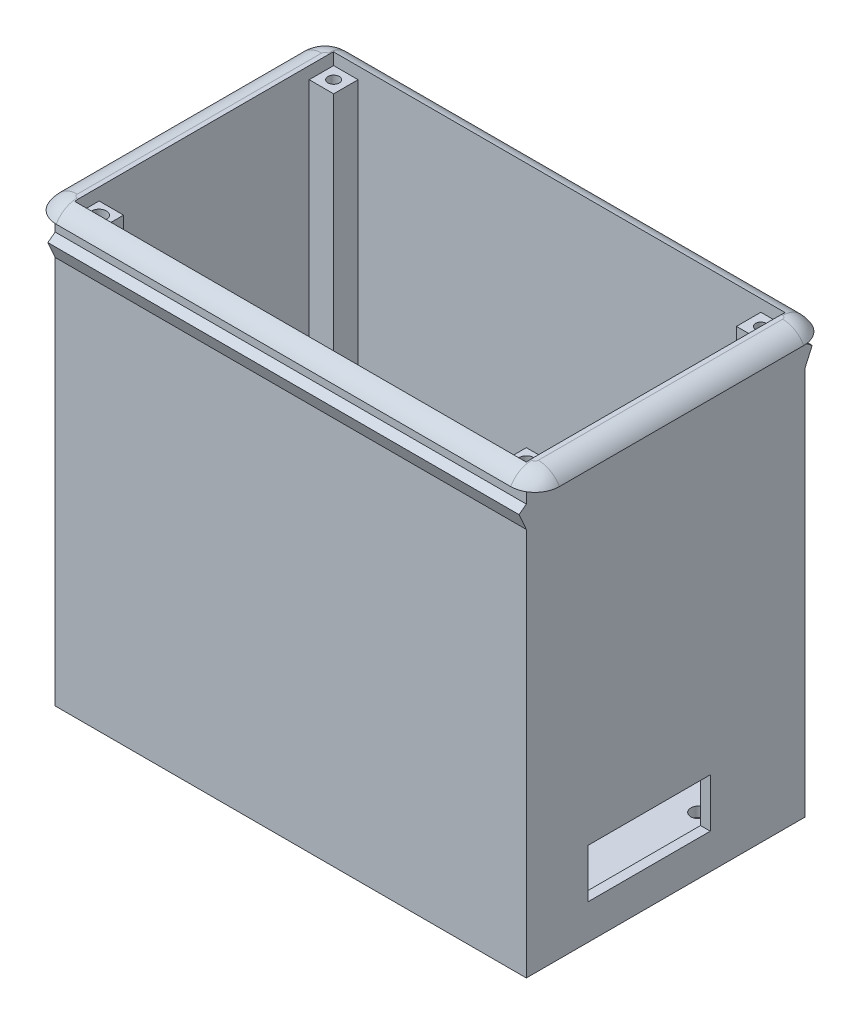
SolidWorks part; units mm, degrees
ref_plane "Front Plane" through (0, 0, 0) normal (0, 0, 1) x (1, 0, 0)
ref_plane "Top Plane" through (0, 0, 0) normal (0, 1, 0) x (1, 0, 0)
ref_plane "Right Plane" through (0, 0, 0) normal (1, 0, 0) x (0, 0, -1)
sketch "Sketch1" plane through (0, 0, 0) normal (0, 1, 0) x (1, 0, 0)
  line L1 (-46.5, 30) -> (46.5, 30)
  line L2 (-51.5, 25) -> (-51.5, -25)
  line L3 (-46.5, -30) -> (46.5, -30)
  line L4 (51.5, 25) -> (51.5, -25)
  line L5 (-51.5, 30) -> (51.5, -30) construction
  line L6 (-51.5, -30) -> (51.5, 30) construction
  arc A0 (46.5, -30) -> (51.5, -25) centre (46.5, -25) ccw
  arc A1 (51.5, 25) -> (46.5, 30) centre (46.5, 25) ccw
  arc A2 (-46.5, -30) -> (-51.5, -25) centre (-46.5, -25) cw
  arc A3 (-46.5, 30) -> (-51.5, 25) centre (-46.5, 25) ccw
  point P0 (0, 0)
  dimension "D3" = 5
  dimension "D1" = 103
  dimension "D2" = 60
extrude "Boss-Extrude1" add sketch "Sketch1" along normal blind 2.5
fillet "Fillet1" radius 5 8 edges at (-50.0355, 2.5, -28.5355) (0, 2.5, -30) (50.0355, 2.5, -28.5355) (51.5, 2.5, 0) (50.0355, 2.5, 28.5355) (0, 2.5, 30) (-50.0355, 2.5, 28.5355) (-51.5, 2.5, 0)
sketch "Sketch2" plane through (0, 0, 0) normal (0, -1, 0) x (1, 0, 0)
  line L0 (0, 30) -> (0, -30) construction
  line L5 (-46.5, 30) -> (46.5, 30) construction
  line L6 (46.5, -30) -> (-46.5, -30) construction
  line L7 (-51.5, 0) -> (51.5, 0) construction
  line L8 (-51.5, -25) -> (-51.5, 25) construction
  line L9 (51.5, 25) -> (51.5, -25) construction
  line L39 (-30.35, 28.5) -> (-30.35, -31.9661) construction
  line L40 (30.35, 28.5) -> (30.35, -35.5794) construction
  line L52 (-48.22, 28.5) -> (48.22, 28.5)
  line L53 (-48.22, 28.5) -> (-48.22, -28.5)
  line L54 (-48.22, -28.5) -> (48.22, -28.5)
  line L55 (48.22, 28.5) -> (48.22, -28.5)
  line L56 (-46.22, 26.5) -> (-46.22, -26.5)
  line L57 (-46.22, -26.5) -> (46.22, -26.5)
  line L58 (46.22, 26.5) -> (46.22, -26.5)
  line L59 (-46.22, 26.5) -> (46.22, 26.5)
  dimension "D1" = 3.28
  dimension "D2" = 3.28
  dimension "D3" = 1.5
  dimension "D4" = 1.5
  dimension "D5" = 2
extrude "Boss-Extrude2" add sketch "Sketch2" along normal blind 85
sketch "Sketch4" plane through (0, 0, 0) normal (0, -1, 0) x (1, 0, 0)
  line L4 (46.22, -26.5) -> (46.22, 26.5)
  line L5 (46.22, 26.5) -> (-46.22, 26.5)
  line L6 (-46.22, 26.5) -> (-46.22, -26.5)
  line L7 (-46.22, -26.5) -> (46.22, -26.5)
  line L8 (46.22, -26.5) -> (46.22, 26.5)
  line L9 (46.22, 26.5) -> (-46.22, 26.5)
  line L10 (-46.22, 26.5) -> (-46.22, -26.5)
  line L11 (-46.22, -26.5) -> (46.22, -26.5)
  dimension "D2" = 53
  dimension "D3" = 92.44
  dimension "D1" = 0
extrude "Cut-Extrude1" cut sketch "Sketch4" against normal through all contours L8 L9 L10 L11
sketch "Sketch3" plane through (0, -85, 0) normal (0, -1, 0) x (1, 0, 0)
  line L4 (-48.22, 28.5) -> (-48.22, -28.5)
  line L5 (-48.22, -28.5) -> (48.22, -28.5)
  line L6 (48.22, -28.5) -> (48.22, 28.5)
  line L7 (48.22, 28.5) -> (-48.22, 28.5)
  line L8 (-48.22, 28.5) -> (-48.22, -28.5)
  line L9 (-48.22, -28.5) -> (48.22, -28.5)
  line L10 (48.22, -28.5) -> (48.22, 28.5)
  line L11 (48.22, 28.5) -> (-48.22, 28.5)
  dimension "D1" = 0
extrude "Boss-Extrude3" add sketch "Sketch3" along normal blind 2
sketch "Sketch5" plane through (-48.22, 0, 0) normal (-1, 0, 0) x (0, 0, 1)
  line L1 (-28.5, -87) -> (-28.5, 0) construction
  line L3 (-28.5, -7.5) -> (-28.5, -3)
  line L4 (-28.5, -3) -> (-30, -4.1147)
  line L5 (-30, -4.1147) -> (-28.5, -7.5)
  dimension "D1" = 4.5
  dimension "D2" = 3
  dimension "D3" = 1.5
extrude "Boss-Extrude4" add sketch "Sketch5" against normal up to surface (96.44 mm away) up to face at (48.22, -43.5, 0)
mirror "Mirror1" about plane through (0, 0, 0) normal (0, 0, 1) of "Boss-Extrude4"
sketch "Sketch6" plane through (0, -85, 0) normal (0, 1, 0) x (1, 0, 0)
  line L0 (0, 26.5) -> (0, -26.5) construction
  line L1 (-46.22, 26.5) -> (46.22, 26.5) construction
  line L2 (46.22, -26.5) -> (-46.22, -26.5) construction
  line L3 (-46.22, 0) -> (46.22, 0) construction
  line L4 (-46.22, -26.5) -> (-46.22, 26.5) construction
  line L5 (46.22, 26.5) -> (46.22, -26.5) construction
  line L6 (46.22, 21.5) -> (41.22, 21.5)
  line L7 (-46.22, 26.5) -> (-41.22, 26.5)
  line L8 (-46.22, 26.5) -> (-46.22, 21.5)
  line L9 (-46.22, 21.5) -> (-41.22, 21.5)
  line L10 (-41.22, 26.5) -> (-41.22, 21.5)
  line L11 (41.22, 26.5) -> (41.22, 21.5)
  line L12 (46.22, 26.5) -> (41.22, 26.5)
  line L13 (46.22, 26.5) -> (46.22, 21.5)
  line L14 (46.22, -26.5) -> (46.22, -21.5)
  line L15 (46.22, -26.5) -> (41.22, -26.5)
  line L16 (41.22, -26.5) -> (41.22, -21.5)
  line L17 (46.22, -21.5) -> (41.22, -21.5)
  line L18 (-46.22, -21.5) -> (-41.22, -21.5)
  line L19 (-41.22, -26.5) -> (-41.22, -21.5)
  line L20 (-46.22, -26.5) -> (-41.22, -26.5)
  line L21 (-46.22, -26.5) -> (-46.22, -21.5)
  dimension "D1" = 5
  dimension "D2" = 5
extrude "Boss-Extrude5" add sketch "Sketch6" along normal offset from surface (85 mm away) 2.5 up to face at (46.6762, 2.5, 0)
sketch "Sketch7" plane through (0, -85, 0) normal (0, 1, 0) x (1, 0, 0)
  line L0 (-46.22, 0) -> (46.22, 0) construction
  line L1 (-46.22, -21.5) -> (-46.22, 21.5) construction
  line L2 (46.22, 21.5) -> (46.22, -21.5) construction
  line L3 (0, 26.5) -> (0, -26.5) construction
  line L4 (46.22, 26.5) -> (-46.22, 26.5) construction
  line L5 (-46.22, -26.5) -> (46.22, -26.5) construction
  circle A0 centre (-38.5, 16.5) radius 1.6
  circle A1 centre (38.5, 16.5) radius 1.6
  circle A2 centre (-38.5, -16.5) radius 1.6
  circle A3 centre (38.5, -16.5) radius 1.6
  dimension "D1" = 3.2
  dimension "D2" = 3.2
  dimension "D3" = 3.2
  dimension "D4" = 3.2
  dimension "D5" = 77
  dimension "D6" = 38.5
  dimension "D7" = 33
  dimension "D8" = 16.5
  dimension "D9" = 77
  dimension "D10" = 33
  dimension "D11" = 16.5
  dimension "D12" = 38.5
extrude "Cut-Extrude2" cut sketch "Sketch7" against normal through all
sketch "Sketch8" plane through (48.22, 0, 0) normal (1, 0, 0) x (0, 0, -1)
  line L1 (-15.8553, -69.8014) -> (9.1447, -69.8014)
  line L2 (-15.8553, -69.8014) -> (-15.8553, -79.8014)
  line L3 (-15.8553, -79.8014) -> (9.1447, -79.8014)
  line L4 (9.1447, -69.8014) -> (9.1447, -79.8014)
  dimension "D1" = 25
  dimension "D2" = 10
extrude "Cut-Extrude3" cut sketch "Sketch8" against normal through all
sketch "Sketch9" plane through (0, 0, 0) normal (0, 1, 0) x (1, 0, 0)
  line L1 (-46.22, -21.5) -> (-46.22, -26.5) construction
  line L2 (-46.22, -26.5) -> (-41.22, -26.5) construction
  line L3 (46.22, -26.5) -> (46.22, -21.5) construction
  line L4 (41.22, -26.5) -> (46.22, -26.5) construction
  line L5 (46.22, 21.5) -> (46.22, 26.5) construction
  line L6 (46.22, 26.5) -> (41.22, 26.5) construction
  line L7 (-41.22, 26.5) -> (-46.22, 26.5) construction
  line L8 (-46.22, 26.5) -> (-46.22, 21.5) construction
  circle A0 centre (-43.72, -24) radius 1.5
  circle A1 centre (43.72, -24) radius 1.5
  circle A2 centre (43.72, 24) radius 1.0835
  circle A3 centre (-43.72, 24) radius 1.1567
  dimension "D1" = 3
  dimension "D4" = 3
  dimension "D2" = 2.5
  dimension "D3" = 2.5
  dimension "D5" = 2.5
  dimension "D6" = 2.5
  dimension "D7" = 2.5
  dimension "D8" = 2.5
  dimension "D9" = 2.5
  dimension "D10" = 2.5
extrude "Cut-Extrude4" cut sketch "Sketch9" against normal through all
